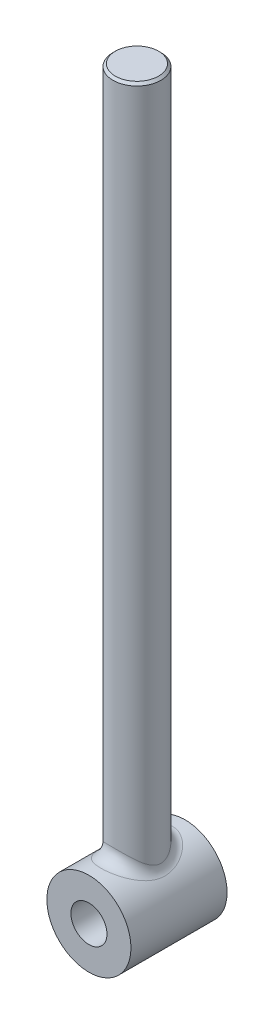
SolidWorks part; units mm, degrees
ref_plane "Front Plane" through (0, 0, 0) normal (0, 0, 1) x (1, 0, 0)
ref_plane "Top Plane" through (0, 0, 0) normal (0, 1, 0) x (1, 0, 0)
ref_plane "Right Plane" through (0, 0, 0) normal (1, 0, 0) x (0, 0, -1)
sketch "Sketch1" plane through (0, 0, 0) normal (0, 0, 1) x (1, 0, 0)
  circle A0 centre (0, 0) radius 7.5
  dimension "D1" = 15
extrude "Extrude-Thin1" add sketch "Sketch1" along normal mid plane 40 thin thin type one direction wall 10
sketch "Sketch2" plane through (0, 0, 0) normal (0, 1, 0) x (1, 0, 0)
  circle A0 centre (0, 0) radius 10
  dimension "D1" = 20
extrude "Boss-Extrude1" add sketch "Sketch2" along normal blind 300
fillet "Fillet1" radius 5 1 edges at (2.9493, 17.2497, 9.5552)
chamfer "Chamfer2" distance 1 angle 45 1 edges at (0, 300, 10)
sketch "Sketch3" plane through (0, 0, 20) normal (0, 0, 1) x (1, 0, 0)
  circle A0 centre (0, 0) radius 7.5 construction
  circle A1 centre (0, 0) radius 7.5
extrude "Cut-Extrude1" cut sketch "Sketch3" against normal blind 300
